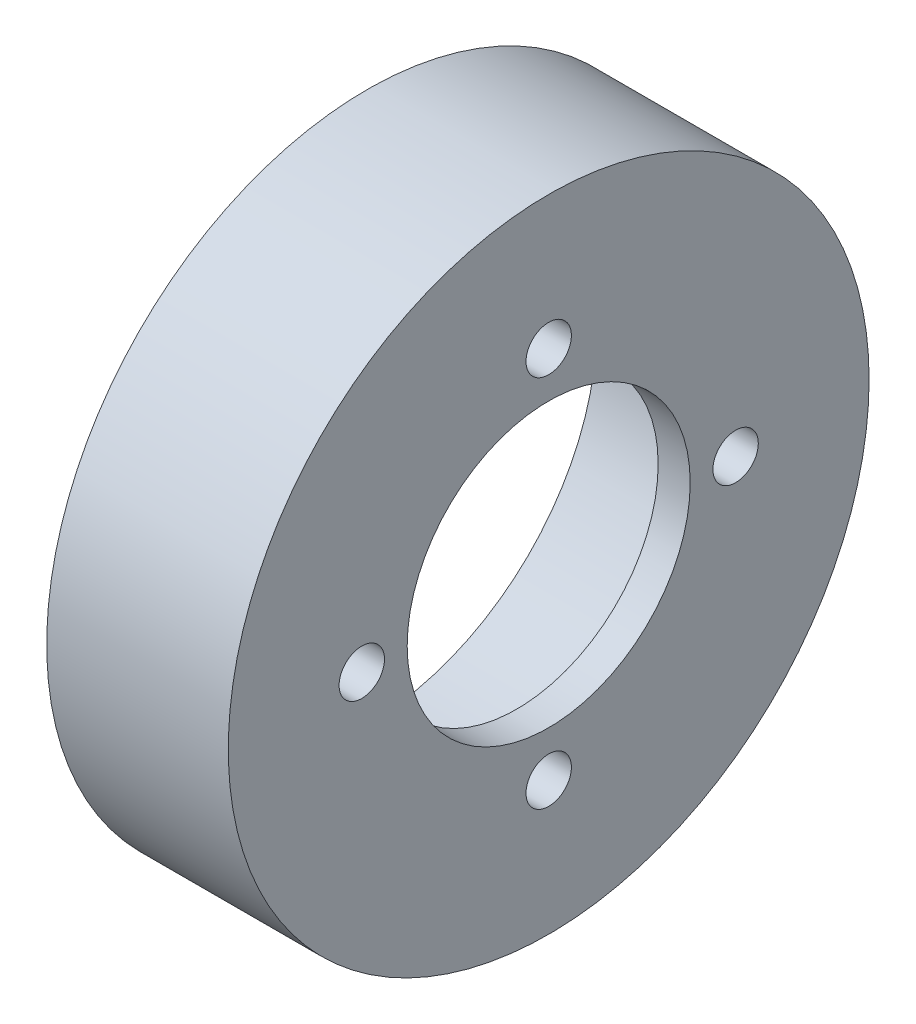
SolidWorks part; units mm, degrees
ref_plane "Front Plane" through (0, 0, 0) normal (0, 0, 1) x (1, 0, 0)
ref_plane "Top Plane" through (0, 0, 0) normal (0, 1, 0) x (1, 0, 0)
ref_plane "Right Plane" through (0, 0, 0) normal (1, 0, 0) x (0, 0, -1)
sketch "Sketch1" plane through (0, 0, 0) normal (1, 0, 0) x (0, 0, -1)
  circle A0 centre (0, 0) radius 21.5
  circle A1 centre (0, 0) radius 30
  dimension "D1" = 43
  dimension "D2" = 60
extrude "Boss-Extrude1" add sketch "Sketch1" along normal blind 14
sketch "Sketch2" plane through (14, 0, 0) normal (1, 0, 0) x (0, 0, -1)
  circle A0 centre (0, 0) radius 30
  circle A1 centre (0, 17.5) radius 2.125
  circle A2 centre (17.5, 0) radius 2.125
  circle A3 centre (0, -17.5) radius 2.125
  circle A4 centre (-17.5, 0) radius 2.125
  circle A5 centre (0, 0) radius 13.25
  point P14 (0, 0)
  dimension "D2" = 4.25
  dimension "D4" = 26.5
  dimension "D1" = 17.5
  dimension "D3" = 4
extrude "Boss-Extrude2" add sketch "Sketch2" along normal blind 3
